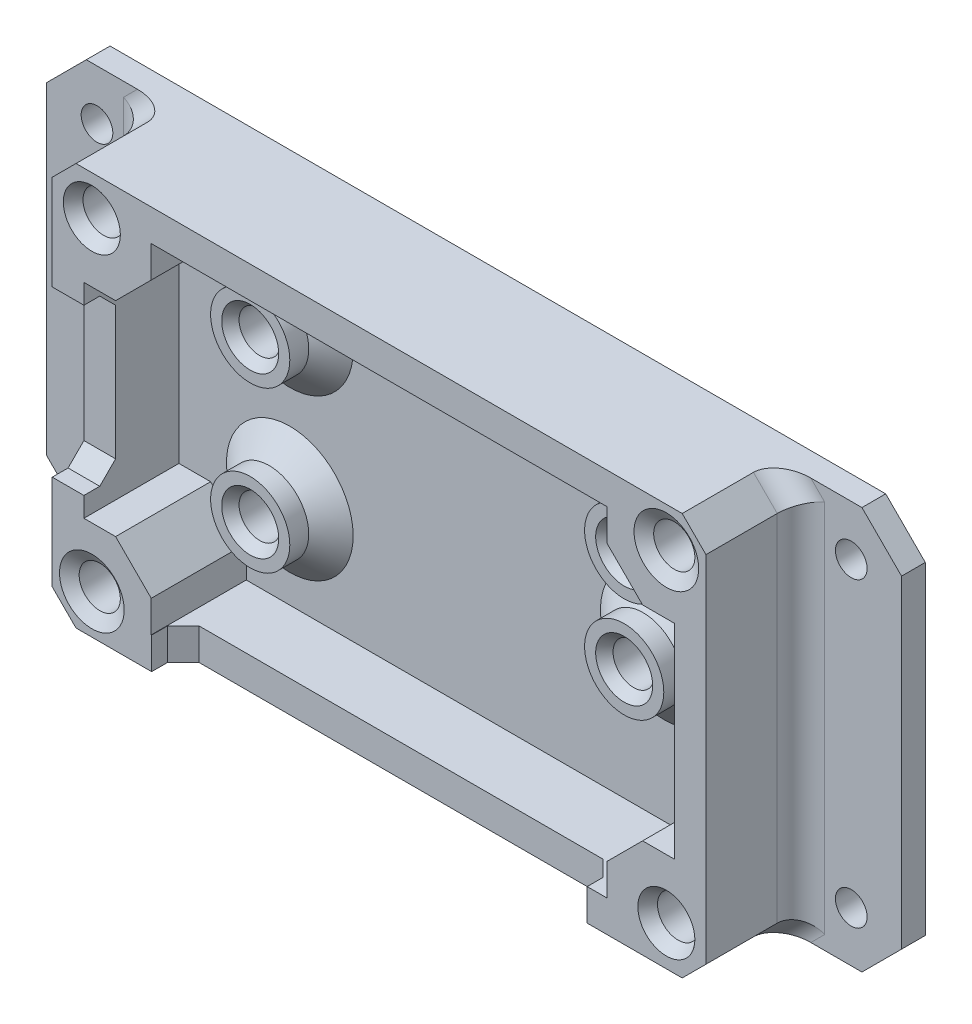
SolidWorks part; units mm, degrees
ref_plane "Front Plane" through (0, 0, 0) normal (0, 0, 1) x (1, 0, 0)
ref_plane "Top Plane" through (0, 0, 0) normal (0, 1, 0) x (1, 0, 0)
ref_plane "Right Plane" through (0, 0, 0) normal (1, 0, 0) x (0, 0, -1)
sketch "Sketch1" plane through (0, 0, 0) normal (0, 0, 1) x (1, 0, 0)
  line L1 (53.975, -25.4) -> (-53.975, -25.4)
  line L2 (53.975, -25.4) -> (53.975, 25.4)
  line L3 (53.975, 25.4) -> (-53.975, 25.4)
  line L4 (-53.975, -25.4) -> (-53.975, 25.4)
  line L5 (53.975, -25.4) -> (-53.975, 25.4) construction
  line L6 (53.975, 25.4) -> (-53.975, -25.4) construction
  point P0 (0, 0)
  dimension "D1" = 107.95
  dimension "D2" = 50.8
extrude "Boss-Extrude1" add sketch "Sketch1" along normal blind 3
sketch "Sketch2" plane through (0, 0, 3) normal (0, 0, 1) x (1, 0, 0)
  line L0 (53.975, 25.4) -> (-53.975, 25.4) construction
  line L1 (41.275, -25.4) -> (-41.275, -25.4)
  line L2 (41.275, -25.4) -> (41.275, 25.4)
  line L3 (41.275, 25.4) -> (-41.275, 25.4)
  line L4 (-41.275, -25.4) -> (-41.275, 25.4)
  line L5 (41.275, -25.4) -> (-41.275, 25.4) construction
  line L6 (41.275, 25.4) -> (-41.275, -25.4) construction
  line L7 (-53.975, 25.4) -> (-53.975, -25.4) construction
  line L8 (-37.275, -21.4) -> (-37.275, 21.4)
  line L9 (37.275, 21.4) -> (-37.275, 21.4)
  line L10 (37.275, -21.4) -> (37.275, 21.4)
  line L11 (37.275, -21.4) -> (-37.275, -21.4)
  point P0 (0, 0)
  dimension "D1" = 12.7
  dimension "D2" = 4
extrude "Boss-Extrude2" add sketch "Sketch2" along normal blind 12
sketch "Sketch3" plane through (0, 0, 3) normal (0, 0, 1) x (1, 0, 0)
  line L0 (41.275, 25.4) -> (-41.275, 25.4) construction
  line L1 (-41.275, 25.4) -> (-41.275, -25.4) construction
  line L2 (-23.275, 10.4) -> (-23.275, -9.823) construction
  line L3 (37.275, 21.4) -> (-37.275, 21.4) construction
  line L4 (23.9512, -2.3) -> (23.9512, 10.4) construction
  line L5 (23.9512, 10.4) -> (-23.275, 10.4) construction
  circle A0 centre (-23.275, 10.4) radius 5
  circle A1 centre (-23.275, -9.823) radius 5
  circle A2 centre (23.9512, 10.4) radius 5
  circle A3 centre (23.9512, -2.3) radius 5
  circle A4 centre (-23.275, 10.4) radius 2.6
  circle A5 centre (-23.275, -9.823) radius 2.6
  circle A6 centre (23.9512, -2.3) radius 2.6
  circle A7 centre (23.9512, 10.4) radius 2.6
  dimension "D1" = 10
  dimension "D2" = 5.2
  dimension "D3" = 15
  dimension "D4" = 18
  dimension "D5" = 47.2262
  dimension "D6" = 12.7
  dimension "D7" = 20.223
extrude "Boss-Extrude3" add sketch "Sketch3" along normal blind 5
sketch "Sketch4" plane through (0, -25.4, 0) normal (0, -1, 0) x (1, 0, 0)
  line L0 (-41.275, 15) -> (41.275, 15) construction
  line L1 (26.275, 15) -> (-28.725, 15)
  line L2 (26.275, 15) -> (26.275, 11)
  line L3 (26.275, 11) -> (-28.725, 11)
  line L4 (-28.725, 15) -> (-28.725, 11)
  line L5 (41.275, 15) -> (41.275, 3) construction
  dimension "D1" = 55
  dimension "D2" = 15
  dimension "D3" = 4
extrude "Cut-Extrude1" cut sketch "Sketch4" against normal up to next
sketch "Sketch5" plane through (-41.275, 0, 0) normal (-1, 0, 0) x (0, 0, 1)
  line L0 (15, 25.4) -> (15, -25.4) construction
  line L1 (15, 10.4) -> (11, 10.4)
  line L2 (15, 10.4) -> (15, -10.4)
  line L3 (15, -10.4) -> (11, -10.4)
  line L4 (11, 10.4) -> (11, -10.4)
  dimension "D1" = 4
  dimension "D2" = 15
  dimension "D3" = 15
extrude "Cut-Extrude2" cut sketch "Sketch5" against normal up to next
sketch "Sketch6" plane through (0, 0, 15) normal (0, 0, 1) x (1, 0, 0)
  line L0 (-41.275, 25.4) -> (-41.275, 10.4) construction
  line L1 (41.275, 25.4) -> (-41.275, 25.4) construction
  line L2 (-28.775, 17.4) -> (-33.275, 12.9)
  line L3 (-33.275, 12.9) -> (-37.275, 12.9)
  line L4 (-37.275, 21.4) -> (-37.275, -21.4) construction
  line L5 (-37.275, 12.9) -> (-37.275, 21.4)
  line L6 (-37.275, 21.4) -> (-28.775, 21.4)
  line L7 (37.275, 21.4) -> (-37.275, 21.4) construction
  line L8 (-28.775, 21.4) -> (-28.775, 17.4)
  line L9 (0, 25.4) -> (0, -25.4) construction
  line L10 (-28.725, -25.4) -> (26.275, -25.4) construction
  line L11 (41.275, 0) -> (-41.275, 0) construction
  line L12 (41.275, -25.4) -> (41.275, 25.4) construction
  line L13 (-41.275, 25.4) -> (-41.275, -25.4) construction
  line L14 (28.775, 21.4) -> (28.775, 17.4)
  line L15 (37.275, 21.4) -> (28.775, 21.4)
  line L16 (37.275, 12.9) -> (37.275, 21.4)
  line L17 (33.275, 12.9) -> (37.275, 12.9)
  line L18 (28.775, 17.4) -> (33.275, 12.9)
  line L19 (28.775, -17.4) -> (33.275, -12.9)
  line L20 (33.275, -12.9) -> (37.275, -12.9)
  line L21 (37.275, -12.9) -> (37.275, -21.4)
  line L22 (37.275, -21.4) -> (28.775, -21.4)
  line L23 (28.775, -21.4) -> (28.775, -17.4)
  line L24 (-28.775, -21.4) -> (-28.775, -17.4)
  line L25 (-37.275, -21.4) -> (-28.775, -21.4)
  line L26 (-37.275, -12.9) -> (-37.275, -21.4)
  line L27 (-33.275, -12.9) -> (-37.275, -12.9)
  line L28 (-28.775, -17.4) -> (-33.275, -12.9)
  circle A0 centre (-36.275, 20.4) radius 2.5
  circle A1 centre (36.275, 20.4) radius 2.5
  circle A2 centre (36.275, -20.4) radius 2.5
  circle A3 centre (-36.275, -20.4) radius 2.5
  line M8 (-37.275, 10.4) -> (-37.275, 21.4)
  line M9 (-37.275, 21.4) -> (37.275, 21.4)
  line M10 (37.275, 21.4) -> (37.275, -21.4)
  line M11 (37.275, -21.4) -> (26.275, -21.4)
  dimension "D1" = 5
  dimension "D2" = 5
  dimension "D3" = 5
  dimension "D4" = 135
  dimension "D5" = 4
  dimension "D6" = 8.5
extrude "Boss-Extrude4" add sketch "Sketch6" against normal up to next contours A0 L3 L2 L8 L6 M8 | L26 A3 L25 L24 L28 L27 | A2 L20 L19 L23 L22 M10 | L16 A1 L14 L18 L17 M9 | L5 A0 M9 | A3 L26 L25 | A1 L15 M10 | L21 A2 M11 region at (33.0114, -17.1364, 15) region at (33.0114, 17.1364, 15) region at (-33.0114, 17.1364, 15) region at (-35.6745, 19.7995, 15) region at (35.6745, 19.7995, 15) region at (35.6745, -19.7995, 15) region at (-33.0114, -17.1364, 15) region at (-35.6745, -19.7995, 15)
chamfer "Chamfer1" distance 3 angle 45 4 edges at (-41.275, 25.4, 9) (41.275, 25.4, 9) (41.275, -25.4, 9) (-41.275, -25.4, 9)
chamfer "Chamfer2" distance 3 angle 41 4 edges at (28.9512, -2.3, 3) (28.9512, 10.4, 3) (-18.275, -9.823, 3) (-18.275, 10.4, 3) first distance on face at (28.9512, -2.3, 3)
chamfer "Chamfer3" distance 1 angle 50 4 edges at (26.5512, -2.3, 8) (-20.675, -9.823, 8) (26.5512, 10.4, 8) (-20.675, 10.4, 8) first distance on face at (28.9512, -2.3, 8) first distance on face at (-18.275, -9.823, 8) first distance on face at (28.9512, 10.4, 8) first distance on face at (-18.275, 10.4, 8)
sketch "Sketch7" plane through (0, 0, 15) normal (0, 0, 1) x (1, 0, 0)
  line L0 (38.275, 25.4) -> (-38.275, 25.4) construction
  line L1 (-41.275, 22.4) -> (-41.275, 10.4) construction
  line L2 (0, 25.4) -> (0, -25.4) construction
  line L3 (-28.725, -25.4) -> (26.275, -25.4) construction
  line L4 (-41.275, 0) -> (41.275, 0) construction
  line L5 (-41.275, 10.4) -> (-41.275, -10.4) construction
  line L6 (41.275, -22.4) -> (41.275, 22.4) construction
  circle A0 centre (-36.275, 20.4) radius 2.6
  circle A1 centre (-36.275, -20.4) radius 2.6
  circle A2 centre (36.275, -20.4) radius 2.6
  circle A3 centre (36.275, 20.4) radius 2.6
  dimension "D1" = 5
  dimension "D3" = 5.2
  dimension "D2" = 5
extrude "Cut-Extrude3" cut sketch "Sketch7" against normal blind 6 contours A0 | A1 | A3 | A2 region at (-36.275, 20.4, 15) region at (-36.275, -20.4, 15) region at (36.275, -20.4, 15) region at (36.275, 20.4, 15)
chamfer "Chamfer4" distance 2 angle 45 4 edges at (-28.725, -23.4, 11) (26.275, -23.4, 11) (-39.275, -10.4, 11) (-39.275, 10.4, 11)
sketch "Sketch8" plane through (0, 0, 3) normal (0, 0, 1) x (1, 0, 0)
  line L0 (-47.625, 19.05) -> (-47.625, -19.05) construction
  line L1 (47.625, 19.05) -> (47.625, -19.05) construction
  line L2 (53.975, -25.4) -> (53.975, 25.4) construction
  line L3 (-47.625, -19.05) -> (47.625, -19.05) construction
  line L4 (-38.275, 25.4) -> (-53.975, 25.4) construction
  line L5 (-53.975, -25.4) -> (-38.275, -25.4) construction
  line L6 (-47.625, 19.05) -> (47.625, 19.05) construction
  line L8 (-53.975, 25.4) -> (-53.975, -25.4) construction
  circle A0 centre (-47.625, 19.05) radius 2
  circle A1 centre (-47.625, -19.05) radius 2
  circle A2 centre (47.625, 19.05) radius 2
  circle A3 centre (47.625, -19.05) radius 2
  dimension "D1" = 6.35
  dimension "D3" = 4
  dimension "D2" = 6.35
  dimension "D4" = 6.35
  dimension "D5" = 6.35
extrude "Cut-Extrude4" cut sketch "Sketch8" against normal through all
chamfer "Chamfer5" distance 5 angle 45 4 edges at (-53.975, 25.4, 1.5) (53.975, 25.4, 1.5) (53.975, -25.4, 1.5) (-53.975, -25.4, 1.5)
fillet "Fillet1" radius 3 6 edges at (39.775, 23.9, 3) (41.275, 0, 3) (39.775, -23.9, 3) (-39.775, 23.9, 3) (-39.775, -23.9, 3) (-41.275, 0, 3)
chamfer "Chamfer6" distance 1 angle 56 4 edges at (-33.675, -20.4, 15) (38.875, -20.4, 15) (38.875, 20.4, 15) (-33.675, 20.4, 15) first distance on face at (-33.675, -20.4, 9) first distance on face at (8.2568, 3.9273, 15) first distance on face at (38.875, 20.4, 9)
